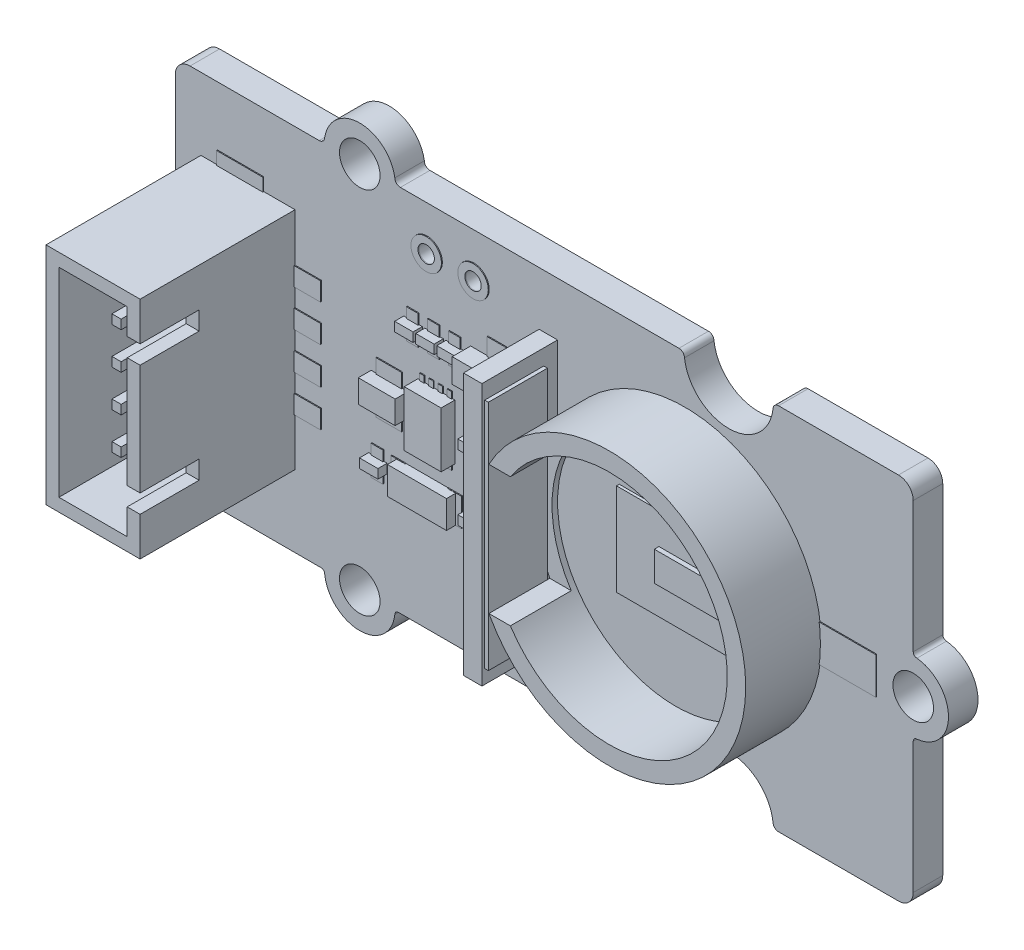
SolidWorks part; units mm, degrees
other "Support_pile_vide"
other "Connecteur_Grove"
other "Carte_Grove_102020083"
ref_plane "Plan de face" through (0, 0, 0) normal (0, 0, 1) x (1, 0, 0)
ref_plane "Plan de dessus" through (0, 0, 0) normal (0, 1, 0) x (1, 0, 0)
ref_plane "Plan de droite" through (0, 0, 0) normal (1, 0, 0) x (0, 0, -1)
sketch "Esquisse1" plane through (0, 0, 0) normal (0, 0, 1) x (1, 0, 0)
  line L0 (20.635, -9.2) -> (20.635, -2.1)
  line L1 (20.635, 2.1) -> (20.635, 9.2)
  line L2 (19.835, 10) -> (13.335, 10)
  line L3 (-18.565, -10) -> (-11.465, -10)
  line L4 (-18.565, 10) -> (-11.565, 10)
  line L5 (-7.165, 10) -> (7.935, 10)
  line L6 (7.935, -10) -> (-7.265, -10)
  line L7 (13.335, -10) -> (19.835, -10)
  line L8 (-19.365, -2.7) -> (-19.365, -9.2)
  line L9 (-19.365, 2.7) -> (-19.365, 9.2)
  arc A0 (-18.565, 10) -> (-19.365, 9.2) centre (-18.565, 9.2) ccw
  arc A1 (-19.365, -9.2) -> (-18.565, -10) centre (-18.565, -9.2) ccw
  arc A2 (19.835, -10) -> (20.635, -9.2) centre (19.835, -9.2) ccw
  arc A3 (20.635, 9.2) -> (19.835, 10) centre (19.835, 9.2) ccw
  arc A4 (13.335, 10) -> (13.035, 9.7) centre (13.335, 9.7) ccw
  arc A5 (-11.465, -10) -> (-11.265, -10.2) centre (-11.465, -10.2) cw
  arc A6 (-7.265, -10) -> (-7.465, -10.2) centre (-7.265, -10.2) ccw
  arc A7 (-7.465, -10.2) -> (-11.265, -10.2) centre (-9.365, -10) cw
  arc A8 (-11.565, 10) -> (-11.265, 10.3) centre (-11.565, 10.3) ccw
  arc A9 (7.935, 10) -> (8.235, 9.7) centre (7.935, 9.7) cw
  arc A10 (-7.165, 10) -> (-7.465, 10.3) centre (-7.165, 10.3) cw
  arc A11 (-11.265, 10.3) -> (-7.465, 10.3) centre (-9.365, 10) cw
  arc A12 (8.235, 9.7) -> (13.035, 9.7) centre (10.635, 10) ccw
  arc A13 (20.635, -2.1) -> (20.835, -1.9) centre (20.835, -2.1) cw
  arc A14 (20.635, 2.1) -> (20.835, 1.9) centre (20.835, 2.1) ccw
  arc A15 (20.835, 1.9) -> (20.835, -1.9) centre (20.635, 0) cw
  arc A16 (7.935, -10) -> (8.235, -9.7) centre (7.935, -9.7) ccw
  arc A17 (13.335, -10) -> (13.035, -9.7) centre (13.335, -9.7) cw
  arc A18 (13.035, -9.7) -> (8.235, -9.7) centre (10.635, -10) ccw
  arc A19 (-19.365, 2.7) -> (-19.065, 2.4) centre (-19.065, 2.7) ccw
  arc A20 (-19.365, -2.7) -> (-19.065, -2.4) centre (-19.065, -2.7) cw
  arc A21 (-19.065, -2.4) -> (-19.065, 2.4) centre (-19.365, 0) ccw
  circle A22 centre (-9.365, -10) radius 1.1
  circle A23 centre (-9.365, 10) radius 1.1
  circle A24 centre (20.635, 0) radius 1.1
  circle A25 centre (4.555, 0) radius 0.75
  circle A26 centre (11.955, 0) radius 0.75
  circle A27 centre (-3.175, 7.62) radius 0.4445
  circle A28 centre (-5.715, 7.62) radius 0.4445
extrude "PCB_contour_et_percages_Eagle_ep_ESTIMEE_1_6" add sketch "Esquisse1" along normal blind 1.6 separate body
sketch "Esquisse2" plane through (0, 0, 0) normal (0, 0, 1) x (1, 0, 0)
  line L1 (-17.973, -6.1) -> (-12.873, -6.1)
  line L2 (-17.973, -6.1) -> (-17.973, 6.1)
  line L3 (-17.973, 6.1) -> (-12.873, 6.1)
  line L4 (-12.873, -6.1) -> (-12.873, 6.1)
extrude "Connecteur_Grove_H_ESTIMEE" add sketch "Esquisse2" along normal blind 8.4 from offset 1.6 separate body
sketch "Esquisse3" plane through (0, 0, 0) normal (0, 0, 1) x (1, 0, 0)
  line L1 (-17.273, -5.4) -> (-13.573, -5.4)
  line L2 (-17.273, -5.4) -> (-17.273, 5.4)
  line L3 (-17.273, 5.4) -> (-13.573, 5.4)
  line L4 (-13.573, -5.4) -> (-13.573, 5.4)
extrude "Cavite_Grove" cut sketch "Esquisse3" against normal blind 7.3 from offset 10
sketch "Esquisse4" plane through (0, 0, 0) normal (0, 0, 1) x (1, 0, 0)
  line L1 (-13.673, -4) -> (-12.673, -4)
  line L2 (-13.673, -4) -> (-13.673, -3)
  line L3 (-13.673, -3) -> (-12.673, -3)
  line L4 (-12.673, -4) -> (-12.673, -3)
  line L6 (-13.673, 3) -> (-12.673, 3)
  line L7 (-13.673, 3) -> (-13.673, 4)
  line L8 (-13.673, 4) -> (-12.673, 4)
  line L9 (-12.673, 3) -> (-12.673, 4)
extrude "Detrompeurs_simplifies" cut sketch "Esquisse4" against normal blind 3.2 from offset 10
sketch "Esquisse5" plane through (0, 0, 0) normal (0, 0, 1) x (1, 0, 0)
  line L1 (-15.8, -3.25) -> (-15.3, -3.25)
  line L2 (-15.8, -3.25) -> (-15.8, -2.75)
  line L3 (-15.8, -2.75) -> (-15.3, -2.75)
  line L4 (-15.3, -3.25) -> (-15.3, -2.75)
  line L6 (-15.8, -1.25) -> (-15.3, -1.25)
  line L7 (-15.8, -1.25) -> (-15.8, -0.75)
  line L8 (-15.8, -0.75) -> (-15.3, -0.75)
  line L9 (-15.3, -1.25) -> (-15.3, -0.75)
  line L11 (-15.8, 0.75) -> (-15.3, 0.75)
  line L12 (-15.8, 0.75) -> (-15.8, 1.25)
  line L13 (-15.8, 1.25) -> (-15.3, 1.25)
  line L14 (-15.3, 0.75) -> (-15.3, 1.25)
  line L16 (-15.8, 2.75) -> (-15.3, 2.75)
  line L17 (-15.8, 2.75) -> (-15.8, 3.25)
  line L18 (-15.8, 3.25) -> (-15.3, 3.25)
  line L19 (-15.3, 2.75) -> (-15.3, 3.25)
extrude "Broches_Grove_pas2" add sketch "Esquisse5" along normal blind 5.9 from offset 2.7 separate body
sketch "Esquisse6" plane through (0, 0, 0) normal (0, 0, 1) x (1, 0, 0)
  circle A0 centre (8.255, 0) radius 7.4
  circle A1 centre (8.255, 0) radius 6.4
extrude "Support_pile_contour_Eagle_H4_1" add sketch "Esquisse6" along normal blind 4.1 from offset 1.6 separate body
sketch "Esquisse7" plane through (0, 0, 0) normal (0, 0, 1) x (1, 0, 0)
  line L1 (0.2, -3.5) -> (4.2, -3.5)
  line L2 (0.2, -3.5) -> (0.2, 3.5)
  line L3 (0.2, 3.5) -> (4.2, 3.5)
  line L4 (4.2, -3.5) -> (4.2, 3.5)
extrude "Ouverture_support_ESTIMEE" cut sketch "Esquisse7" against normal blind 3.3 from offset 5.7
sketch "Esquisse8" plane through (0, 0, 0) normal (0, 0, 1) x (1, 0, 0)
  circle A0 centre (8.255, 0) radius 6.4
extrude "Fond_support_simplifie" add sketch "Esquisse8" along normal blind 0.5 from offset 1.6 separate body
sketch "Esquisse9" plane through (0, 0, 0) normal (0, 0, 1) x (1, 0, 0)
  line L1 (0.355, -7.1) -> (1.355, -7.1)
  line L2 (0.355, -7.1) -> (0.355, 7.1)
  line L3 (0.355, 7.1) -> (1.355, 7.1)
  line L4 (1.355, -7.1) -> (1.355, 7.1)
extrude "Dos_support_pile_ESTIME" add sketch "Esquisse9" along normal blind 4.1 from offset 1.6 separate body
sketch "Esquisse10" plane through (0, 0, 0) normal (0, 0, 1) x (1, 0, 0)
  line L1 (1.405, -6.3) -> (1.605, -6.3)
  line L2 (1.405, -6.3) -> (1.405, 6.3)
  line L3 (1.405, 6.3) -> (1.605, 6.3)
  line L4 (1.605, -6.3) -> (1.605, 6.3)
extrude "Contact_positif_support_simplifie" add sketch "Esquisse10" along normal blind 3.2 from offset 2.4 separate body
sketch "Esquisse11" plane through (0, 0, 0) normal (0, 0, 1) x (1, 0, 0)
  line L1 (5.2, -2.5) -> (12.9, -2.5)
  line L2 (5.2, -2.5) -> (5.2, 2.5)
  line L3 (5.2, 2.5) -> (12.9, 2.5)
  line L4 (12.9, -2.5) -> (12.9, 2.5)
extrude "Contact_fond_support_simplifie" add sketch "Esquisse11" along normal blind 0.15 from offset 2.1 separate body
sketch "Esquisse12" plane through (0, 0, 0) normal (0, 0, 1) x (1, 0, 0)
  line L1 (7.5, -0.8) -> (12, -0.8)
  line L2 (7.5, -0.8) -> (7.5, 0.8)
  line L3 (7.5, 0.8) -> (12, 0.8)
  line L4 (12, -0.8) -> (12, 0.8)
extrude "Lame_ressort_simplifiee" add sketch "Esquisse12" along normal blind 0.25 from offset 2.25 separate body
sketch "Esquisse13" plane through (0, 0, 0) normal (0, 0, 1) x (1, 0, 0)
  line L1 (-7.315, -4.306) -> (-4.115, -4.306)
  line L2 (-7.315, -4.306) -> (-7.315, -2.806)
  line L3 (-7.315, -2.806) -> (-4.115, -2.806)
  line L4 (-4.115, -4.306) -> (-4.115, -2.806)
extrude "X1_position_Eagle" add sketch "Esquisse13" along normal blind 0.55 from offset 1.6 separate body
sketch "Esquisse14" plane through (0, 0, 0) normal (0, 0, 1) x (1, 0, 0)
  line L1 (-6.207, -1.5) -> (-4.207, -1.5)
  line L2 (-6.207, -1.5) -> (-6.207, 1.5)
  line L3 (-6.207, 1.5) -> (-4.207, 1.5)
  line L4 (-4.207, -1.5) -> (-4.207, 1.5)
extrude "U2_position_Eagle" add sketch "Esquisse14" along normal blind 0.75 from offset 1.6 separate body
sketch "Esquisse15" plane through (0, 0, 0) normal (0, 0, 1) x (1, 0, 0)
  line L1 (-8.882, -3.806) -> (-7.882, -3.806)
  line L2 (-8.882, -3.806) -> (-8.882, -3.306)
  line L3 (-8.882, -3.306) -> (-7.882, -3.306)
  line L4 (-7.882, -3.806) -> (-7.882, -3.306)
extrude "C1_position_Eagle" add sketch "Esquisse15" along normal blind 0.5 from offset 1.6 separate body
sketch "Esquisse16" plane through (0, 0, 0) normal (0, 0, 1) x (1, 0, 0)
  line L1 (-3.548, -3.806) -> (-2.548, -3.806)
  line L2 (-3.548, -3.806) -> (-3.548, -3.306)
  line L3 (-3.548, -3.306) -> (-2.548, -3.306)
  line L4 (-2.548, -3.806) -> (-2.548, -3.306)
extrude "C3_position_Eagle" add sketch "Esquisse16" along normal blind 0.5 from offset 1.6 separate body
sketch "Esquisse17" plane through (0, 0, 0) normal (0, 0, 1) x (1, 0, 0)
  line L1 (-5.834, 3.56) -> (-4.834, 3.56)
  line L2 (-5.834, 3.56) -> (-5.834, 4.06)
  line L3 (-5.834, 4.06) -> (-4.834, 4.06)
  line L4 (-4.834, 3.56) -> (-4.834, 4.06)
extrude "R1_position_Eagle" add sketch "Esquisse17" along normal blind 0.5 from offset 1.6 separate body
sketch "Esquisse18" plane through (0, 0, 0) normal (0, 0, 1) x (1, 0, 0)
  line L1 (-3.548, -0.25) -> (-2.548, -0.25)
  line L2 (-3.548, -0.25) -> (-3.548, 0.25)
  line L3 (-3.548, 0.25) -> (-2.548, 0.25)
  line L4 (-2.548, -0.25) -> (-2.548, 0.25)
extrude "R3_position_Eagle" add sketch "Esquisse18" along normal blind 0.5 from offset 1.6 separate body
sketch "Esquisse19" plane through (0, 0, 0) normal (0, 0, 1) x (1, 0, 0)
  line L1 (-3.355, 3.16) -> (-0.455, 3.16)
  line L2 (-3.355, 3.16) -> (-3.355, 4.46)
  line L3 (-3.355, 4.46) -> (-0.455, 4.46)
  line L4 (-0.455, 3.16) -> (-0.455, 4.46)
extrude "U1_position_Eagle" add sketch "Esquisse19" along normal blind 1 from offset 1.6 separate body
sketch "Esquisse20" plane through (0, 0, 0) normal (0, 0, 1) x (1, 0, 0)
  line L1 (-6.977, 3.56) -> (-5.977, 3.56)
  line L2 (-6.977, 3.56) -> (-6.977, 4.06)
  line L3 (-6.977, 4.06) -> (-5.977, 4.06)
  line L4 (-5.977, 3.56) -> (-5.977, 4.06)
extrude "C2_position_Eagle" add sketch "Esquisse20" along normal blind 0.5 from offset 1.6 separate body
sketch "Esquisse21" plane through (0, 0, 0) normal (0, 0, 1) x (1, 0, 0)
  line L1 (-4.691, 3.56) -> (-3.691, 3.56)
  line L2 (-4.691, 3.56) -> (-4.691, 4.06)
  line L3 (-4.691, 4.06) -> (-3.691, 4.06)
  line L4 (-3.691, 3.56) -> (-3.691, 4.06)
extrude "R2_position_Eagle" add sketch "Esquisse21" along normal blind 0.5 from offset 1.6 separate body
sketch "Esquisse22" plane through (0, 0, 0) normal (0, 0, 1) x (1, 0, 0)
  line L1 (-8.747, -0.625) -> (-6.747, -0.625)
  line L2 (-8.747, -0.625) -> (-8.747, 0.625)
  line L3 (-8.747, 0.625) -> (-6.747, 0.625)
  line L4 (-6.747, -0.625) -> (-6.747, 0.625)
extrude "C4_position_Eagle" add sketch "Esquisse22" along normal blind 0.7 from offset 1.6 separate body
sketch "Esquisse23" plane through (0, 0, 0) normal (0, 0, 1) x (1, 0, 0)
  line L1 (-4.572, -4.318) -> (-3.81, -4.318)
  line L2 (-4.572, -4.318) -> (-4.572, -2.794)
  line L3 (-4.572, -2.794) -> (-3.81, -2.794)
  line L4 (-3.81, -4.318) -> (-3.81, -2.794)
extrude "Pad_X1_0" add sketch "Esquisse23" along normal blind 0.05 from offset 1.6 separate body
sketch "Esquisse24" plane through (0, 0, 0) normal (0, 0, 1) x (1, 0, 0)
  line L1 (-7.62, -4.318) -> (-6.858, -4.318)
  line L2 (-7.62, -4.318) -> (-7.62, -2.794)
  line L3 (-7.62, -2.794) -> (-6.858, -2.794)
  line L4 (-6.858, -4.318) -> (-6.858, -2.794)
extrude "Pad_X1_1" add sketch "Esquisse24" along normal blind 0.05 from offset 1.6 separate body
sketch "Esquisse25" plane through (0, 0, 0) normal (0, 0, 1) x (1, 0, 0)
  line L1 (-13.95, -3.5) -> (-11.45, -3.5)
  line L2 (-13.95, -3.5) -> (-13.95, -2.5)
  line L3 (-13.95, -2.5) -> (-11.45, -2.5)
  line L4 (-11.45, -3.5) -> (-11.45, -2.5)
extrude "Pad_J1_0" add sketch "Esquisse25" along normal blind 0.05 from offset 1.6 separate body
sketch "Esquisse26" plane through (0, 0, 0) normal (0, 0, 1) x (1, 0, 0)
  line L1 (-13.95, -1.5) -> (-11.45, -1.5)
  line L2 (-13.95, -1.5) -> (-13.95, -0.5)
  line L3 (-13.95, -0.5) -> (-11.45, -0.5)
  line L4 (-11.45, -1.5) -> (-11.45, -0.5)
extrude "Pad_J1_1" add sketch "Esquisse26" along normal blind 0.05 from offset 1.6 separate body
sketch "Esquisse27" plane through (0, 0, 0) normal (0, 0, 1) x (1, 0, 0)
  line L1 (-13.95, 0.5) -> (-11.45, 0.5)
  line L2 (-13.95, 0.5) -> (-13.95, 1.5)
  line L3 (-13.95, 1.5) -> (-11.45, 1.5)
  line L4 (-11.45, 0.5) -> (-11.45, 1.5)
extrude "Pad_J1_2" add sketch "Esquisse27" along normal blind 0.05 from offset 1.6 separate body
sketch "Esquisse28" plane through (0, 0, 0) normal (0, 0, 1) x (1, 0, 0)
  line L1 (-13.95, 2.5) -> (-11.45, 2.5)
  line L2 (-13.95, 2.5) -> (-13.95, 3.5)
  line L3 (-13.95, 3.5) -> (-11.45, 3.5)
  line L4 (-11.45, 2.5) -> (-11.45, 3.5)
extrude "Pad_J1_3" add sketch "Esquisse28" along normal blind 0.05 from offset 1.6 separate body
sketch "Esquisse29" plane through (0, 0, 0) normal (0, 0, 1) x (1, 0, 0)
  line L1 (-17.073, -6.8) -> (-14.573, -6.8)
  line L2 (-17.073, -6.8) -> (-17.073, -4.8)
  line L3 (-17.073, -4.8) -> (-14.573, -4.8)
  line L4 (-14.573, -6.8) -> (-14.573, -4.8)
extrude "Pad_J1_4" add sketch "Esquisse29" along normal blind 0.05 from offset 1.6 separate body
sketch "Esquisse30" plane through (0, 0, 0) normal (0, 0, 1) x (1, 0, 0)
  line L1 (-17.073, 4.8) -> (-14.573, 4.8)
  line L2 (-17.073, 4.8) -> (-17.073, 6.8)
  line L3 (-17.073, 6.8) -> (-14.573, 6.8)
  line L4 (-14.573, 4.8) -> (-14.573, 6.8)
extrude "Pad_J1_5" add sketch "Esquisse30" along normal blind 0.05 from offset 1.6 separate body
sketch "Esquisse31" plane through (0, 0, 0) normal (0, 0, 1) x (1, 0, 0)
  line L1 (-6.082, -1.85) -> (-5.832, -1.85)
  line L2 (-6.082, -1.85) -> (-6.082, -1.15)
  line L3 (-6.082, -1.15) -> (-5.832, -1.15)
  line L4 (-5.832, -1.85) -> (-5.832, -1.15)
extrude "Pad_U2_0" add sketch "Esquisse31" along normal blind 0.05 from offset 1.6 separate body
sketch "Esquisse32" plane through (0, 0, 0) normal (0, 0, 1) x (1, 0, 0)
  line L1 (-5.582, -1.85) -> (-5.332, -1.85)
  line L2 (-5.582, -1.85) -> (-5.582, -1.15)
  line L3 (-5.582, -1.15) -> (-5.332, -1.15)
  line L4 (-5.332, -1.85) -> (-5.332, -1.15)
extrude "Pad_U2_1" add sketch "Esquisse32" along normal blind 0.05 from offset 1.6 separate body
sketch "Esquisse33" plane through (0, 0, 0) normal (0, 0, 1) x (1, 0, 0)
  line L1 (-5.082, -1.85) -> (-4.832, -1.85)
  line L2 (-5.082, -1.85) -> (-5.082, -1.15)
  line L3 (-5.082, -1.15) -> (-4.832, -1.15)
  line L4 (-4.832, -1.85) -> (-4.832, -1.15)
extrude "Pad_U2_2" add sketch "Esquisse33" along normal blind 0.05 from offset 1.6 separate body
sketch "Esquisse34" plane through (0, 0, 0) normal (0, 0, 1) x (1, 0, 0)
  line L1 (-4.582, -1.85) -> (-4.332, -1.85)
  line L2 (-4.582, -1.85) -> (-4.582, -1.15)
  line L3 (-4.582, -1.15) -> (-4.332, -1.15)
  line L4 (-4.332, -1.85) -> (-4.332, -1.15)
extrude "Pad_U2_3" add sketch "Esquisse34" along normal blind 0.05 from offset 1.6 separate body
sketch "Esquisse35" plane through (0, 0, 0) normal (0, 0, 1) x (1, 0, 0)
  line L1 (-4.582, 1.15) -> (-4.332, 1.15)
  line L2 (-4.582, 1.15) -> (-4.582, 1.85)
  line L3 (-4.582, 1.85) -> (-4.332, 1.85)
  line L4 (-4.332, 1.15) -> (-4.332, 1.85)
extrude "Pad_U2_4" add sketch "Esquisse35" along normal blind 0.05 from offset 1.6 separate body
sketch "Esquisse36" plane through (0, 0, 0) normal (0, 0, 1) x (1, 0, 0)
  line L1 (-5.082, 1.15) -> (-4.832, 1.15)
  line L2 (-5.082, 1.15) -> (-5.082, 1.85)
  line L3 (-5.082, 1.85) -> (-4.832, 1.85)
  line L4 (-4.832, 1.15) -> (-4.832, 1.85)
extrude "Pad_U2_5" add sketch "Esquisse36" along normal blind 0.05 from offset 1.6 separate body
sketch "Esquisse37" plane through (0, 0, 0) normal (0, 0, 1) x (1, 0, 0)
  line L1 (-5.582, 1.15) -> (-5.332, 1.15)
  line L2 (-5.582, 1.15) -> (-5.582, 1.85)
  line L3 (-5.582, 1.85) -> (-5.332, 1.85)
  line L4 (-5.332, 1.15) -> (-5.332, 1.85)
extrude "Pad_U2_6" add sketch "Esquisse37" along normal blind 0.05 from offset 1.6 separate body
sketch "Esquisse38" plane through (0, 0, 0) normal (0, 0, 1) x (1, 0, 0)
  line L1 (-6.082, 1.15) -> (-5.832, 1.15)
  line L2 (-6.082, 1.15) -> (-6.082, 1.85)
  line L3 (-6.082, 1.85) -> (-5.832, 1.85)
  line L4 (-5.832, 1.15) -> (-5.832, 1.85)
extrude "Pad_U2_7" add sketch "Esquisse38" along normal blind 0.05 from offset 1.6 separate body
sketch "Esquisse39" plane through (0, 0, 0) normal (0, 0, 1) x (1, 0, 0)
  line L1 (-5.957, -0.75) -> (-4.457, -0.75)
  line L2 (-5.957, -0.75) -> (-5.957, 0.75)
  line L3 (-5.957, 0.75) -> (-4.457, 0.75)
  line L4 (-4.457, -0.75) -> (-4.457, 0.75)
extrude "Pad_U2_8" add sketch "Esquisse39" along normal blind 0.05 from offset 1.6 separate body
sketch "Esquisse40" plane through (0, 0, 0) normal (0, 0, 1) x (1, 0, 0)
  line L1 (-8.6995, -4.358) -> (-8.0645, -4.358)
  line L2 (-8.6995, -4.358) -> (-8.6995, -3.723)
  line L3 (-8.6995, -3.723) -> (-8.0645, -3.723)
  line L4 (-8.0645, -4.358) -> (-8.0645, -3.723)
extrude "Pad_C1_0" add sketch "Esquisse40" along normal blind 0.05 from offset 1.6 separate body
sketch "Esquisse41" plane through (0, 0, 0) normal (0, 0, 1) x (1, 0, 0)
  line L1 (-8.6995, -3.389) -> (-8.0645, -3.389)
  line L2 (-8.6995, -3.389) -> (-8.6995, -2.754)
  line L3 (-8.6995, -2.754) -> (-8.0645, -2.754)
  line L4 (-8.0645, -3.389) -> (-8.0645, -2.754)
extrude "Pad_C1_1" add sketch "Esquisse41" along normal blind 0.05 from offset 1.6 separate body
sketch "Esquisse42" plane through (0, 0, 0) normal (0, 0, 1) x (1, 0, 0)
  line L1 (-3.3655, -4.358) -> (-2.7305, -4.358)
  line L2 (-3.3655, -4.358) -> (-3.3655, -3.723)
  line L3 (-3.3655, -3.723) -> (-2.7305, -3.723)
  line L4 (-2.7305, -4.358) -> (-2.7305, -3.723)
extrude "Pad_C3_0" add sketch "Esquisse42" along normal blind 0.05 from offset 1.6 separate body
sketch "Esquisse43" plane through (0, 0, 0) normal (0, 0, 1) x (1, 0, 0)
  line L1 (-3.3655, -3.389) -> (-2.7305, -3.389)
  line L2 (-3.3655, -3.389) -> (-3.3655, -2.754)
  line L3 (-3.3655, -2.754) -> (-2.7305, -2.754)
  line L4 (-2.7305, -3.389) -> (-2.7305, -2.754)
extrude "Pad_C3_1" add sketch "Esquisse43" along normal blind 0.05 from offset 1.6 separate body
sketch "Esquisse44" plane through (0, 0, 0) normal (0, 0, 1) x (1, 0, 0)
  line L1 (-5.6515, 3.008) -> (-5.0165, 3.008)
  line L2 (-5.6515, 3.008) -> (-5.6515, 3.643)
  line L3 (-5.6515, 3.643) -> (-5.0165, 3.643)
  line L4 (-5.0165, 3.008) -> (-5.0165, 3.643)
extrude "Pad_R1_0" add sketch "Esquisse44" along normal blind 0.05 from offset 1.6 separate body
sketch "Esquisse45" plane through (0, 0, 0) normal (0, 0, 1) x (1, 0, 0)
  line L1 (-5.6515, 3.977) -> (-5.0165, 3.977)
  line L2 (-5.6515, 3.977) -> (-5.6515, 4.612)
  line L3 (-5.6515, 4.612) -> (-5.0165, 4.612)
  line L4 (-5.0165, 3.977) -> (-5.0165, 4.612)
extrude "Pad_R1_1" add sketch "Esquisse45" along normal blind 0.05 from offset 1.6 separate body
sketch "Esquisse46" plane through (0, 0, 0) normal (0, 0, 1) x (1, 0, 0)
  line L1 (-3.3655, 0.167) -> (-2.7305, 0.167)
  line L2 (-3.3655, 0.167) -> (-3.3655, 0.802)
  line L3 (-3.3655, 0.802) -> (-2.7305, 0.802)
  line L4 (-2.7305, 0.167) -> (-2.7305, 0.802)
extrude "Pad_R3_0" add sketch "Esquisse46" along normal blind 0.05 from offset 1.6 separate body
sketch "Esquisse47" plane through (0, 0, 0) normal (0, 0, 1) x (1, 0, 0)
  line L1 (-3.3655, -0.802) -> (-2.7305, -0.802)
  line L2 (-3.3655, -0.802) -> (-3.3655, -0.167)
  line L3 (-3.3655, -0.167) -> (-2.7305, -0.167)
  line L4 (-2.7305, -0.802) -> (-2.7305, -0.167)
extrude "Pad_R3_1" add sketch "Esquisse47" along normal blind 0.05 from offset 1.6 separate body
sketch "Esquisse48" plane through (0, 0, 0) normal (0, 0, 1) x (1, 0, 0)
  line L1 (-2.413, 4.2545) -> (-1.397, 4.2545)
  line L2 (-2.413, 4.2545) -> (-2.413, 5.3975)
  line L3 (-2.413, 5.3975) -> (-1.397, 5.3975)
  line L4 (-1.397, 4.2545) -> (-1.397, 5.3975)
extrude "Pad_U1_0" add sketch "Esquisse48" along normal blind 0.05 from offset 1.6 separate body
sketch "Esquisse49" plane through (0, 0, 0) normal (0, 0, 1) x (1, 0, 0)
  line L1 (-1.524, 2.2225) -> (-0.508, 2.2225)
  line L2 (-1.524, 2.2225) -> (-1.524, 3.3655)
  line L3 (-1.524, 3.3655) -> (-0.508, 3.3655)
  line L4 (-0.508, 2.2225) -> (-0.508, 3.3655)
extrude "Pad_U1_1" add sketch "Esquisse49" along normal blind 0.05 from offset 1.6 separate body
sketch "Esquisse50" plane through (0, 0, 0) normal (0, 0, 1) x (1, 0, 0)
  line L1 (-3.302, 2.2225) -> (-2.286, 2.2225)
  line L2 (-3.302, 2.2225) -> (-3.302, 3.3655)
  line L3 (-3.302, 3.3655) -> (-2.286, 3.3655)
  line L4 (-2.286, 2.2225) -> (-2.286, 3.3655)
extrude "Pad_U1_2" add sketch "Esquisse50" along normal blind 0.05 from offset 1.6 separate body
sketch "Esquisse51" plane through (0, 0, 0) normal (0, 0, 1) x (1, 0, 0)
  line L1 (-6.7945, 3.008) -> (-6.1595, 3.008)
  line L2 (-6.7945, 3.008) -> (-6.7945, 3.643)
  line L3 (-6.7945, 3.643) -> (-6.1595, 3.643)
  line L4 (-6.1595, 3.008) -> (-6.1595, 3.643)
extrude "Pad_C2_0" add sketch "Esquisse51" along normal blind 0.05 from offset 1.6 separate body
sketch "Esquisse52" plane through (0, 0, 0) normal (0, 0, 1) x (1, 0, 0)
  line L1 (-6.7945, 3.977) -> (-6.1595, 3.977)
  line L2 (-6.7945, 3.977) -> (-6.7945, 4.612)
  line L3 (-6.7945, 4.612) -> (-6.1595, 4.612)
  line L4 (-6.1595, 3.977) -> (-6.1595, 4.612)
extrude "Pad_C2_1" add sketch "Esquisse52" along normal blind 0.05 from offset 1.6 separate body
sketch "Esquisse53" plane through (0, 0, 0) normal (0, 0, 1) x (1, 0, 0)
  line L1 (-4.5085, 3.008) -> (-3.8735, 3.008)
  line L2 (-4.5085, 3.008) -> (-4.5085, 3.643)
  line L3 (-4.5085, 3.643) -> (-3.8735, 3.643)
  line L4 (-3.8735, 3.008) -> (-3.8735, 3.643)
extrude "Pad_R2_0" add sketch "Esquisse53" along normal blind 0.05 from offset 1.6 separate body
sketch "Esquisse54" plane through (0, 0, 0) normal (0, 0, 1) x (1, 0, 0)
  line L1 (-4.5085, 3.977) -> (-3.8735, 3.977)
  line L2 (-4.5085, 3.977) -> (-4.5085, 4.612)
  line L3 (-4.5085, 4.612) -> (-3.8735, 4.612)
  line L4 (-3.8735, 3.977) -> (-3.8735, 4.612)
extrude "Pad_R2_1" add sketch "Esquisse54" along normal blind 0.05 from offset 1.6 separate body
sketch "Esquisse55" plane through (0, 0, 0) normal (0, 0, 1) x (1, 0, 0)
  line L1 (-2.145, -1) -> (2.255, -1)
  line L2 (-2.145, -1) -> (-2.145, 1)
  line L3 (-2.145, 1) -> (2.255, 1)
  line L4 (2.255, -1) -> (2.255, 1)
extrude "Pad_BAT1_0" add sketch "Esquisse55" along normal blind 0.05 from offset 1.6 separate body
sketch "Esquisse56" plane through (0, 0, 0) normal (0, 0, 1) x (1, 0, 0)
  line L1 (14.255, -1) -> (18.655, -1)
  line L2 (14.255, -1) -> (14.255, 1)
  line L3 (14.255, 1) -> (18.655, 1)
  line L4 (18.655, -1) -> (18.655, 1)
extrude "Pad_BAT1_1" add sketch "Esquisse56" along normal blind 0.05 from offset 1.6 separate body
sketch "Esquisse57" plane through (0, 0, 0) normal (0, 0, 1) x (1, 0, 0)
  line L1 (-8.4455, -1.397) -> (-7.0485, -1.397)
  line L2 (-8.4455, -1.397) -> (-8.4455, -0.381)
  line L3 (-8.4455, -0.381) -> (-7.0485, -0.381)
  line L4 (-7.0485, -1.397) -> (-7.0485, -0.381)
extrude "Pad_C4_0" add sketch "Esquisse57" along normal blind 0.05 from offset 1.6 separate body
sketch "Esquisse58" plane through (0, 0, 0) normal (0, 0, 1) x (1, 0, 0)
  line L1 (-8.4455, 0.381) -> (-7.0485, 0.381)
  line L2 (-8.4455, 0.381) -> (-8.4455, 1.397)
  line L3 (-8.4455, 1.397) -> (-7.0485, 1.397)
  line L4 (-7.0485, 0.381) -> (-7.0485, 1.397)
extrude "Pad_C4_1" add sketch "Esquisse58" along normal blind 0.05 from offset 1.6 separate body
sketch "Esquisse59" plane through (0, 0, 0) normal (0, 0, 1) x (1, 0, 0)
  circle A0 centre (-3.175, 7.62) radius 0.8255
  circle A1 centre (-3.175, 7.62) radius 0.4445
  circle A2 centre (-5.715, 7.62) radius 0.8255
  circle A3 centre (-5.715, 7.62) radius 0.4445
extrude "Anneaux_CLK_INT" add sketch "Esquisse59" along normal blind 0.05 from offset 1.6 separate body
